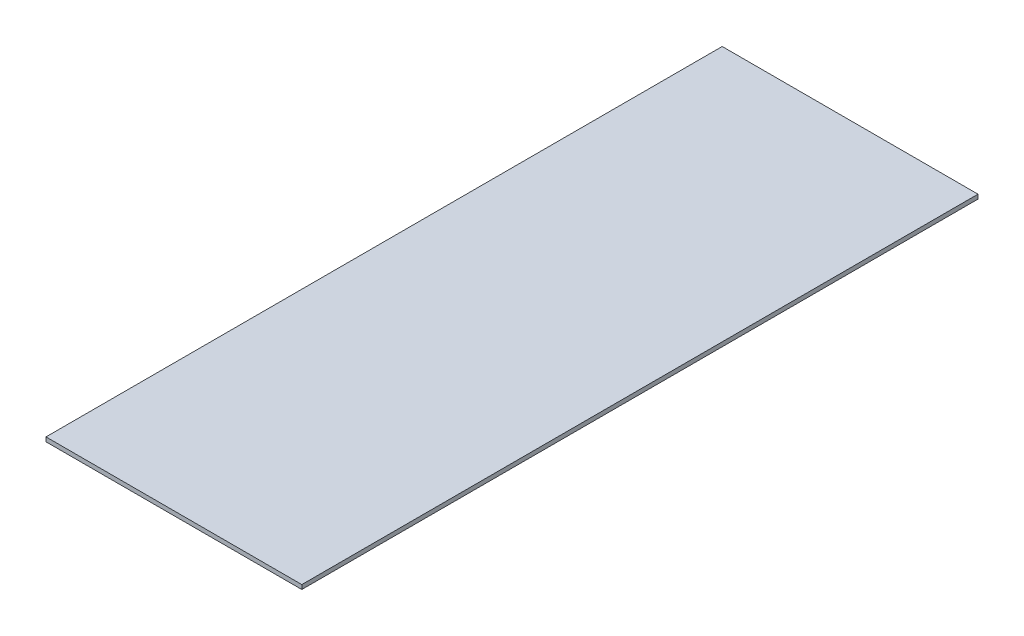
SolidWorks part; units mm, degrees
ref_plane "前视基准面" through (0, 0, 0) normal (0, 0, 1) x (1, 0, 0)
ref_plane "上视基准面" through (0, 0, 0) normal (0, 1, 0) x (1, 0, 0)
ref_plane "右视基准面" through (0, 0, 0) normal (1, 0, 0) x (0, 0, -1)
other "Configuration Table"
sketch "草图1" plane through (0, 0, 0) normal (0, 1, 0) x (1, 0, 0)
  line L1 (-89.53, 236.665) -> (89.53, 236.665)
  line L2 (-89.53, 236.665) -> (-89.53, -236.665)
  line L3 (-89.53, -236.665) -> (89.53, -236.665)
  line L4 (89.53, 236.665) -> (89.53, -236.665)
  line L5 (-89.53, 236.665) -> (89.53, -236.665) construction
  line L6 (-89.53, -236.665) -> (89.53, 236.665) construction
  point P0 (0, 0)
  dimension "D1" = 179.06
  dimension "D2" = 473.33
extrude "凸台-拉伸1" add sketch "草图1" along normal blind 3
